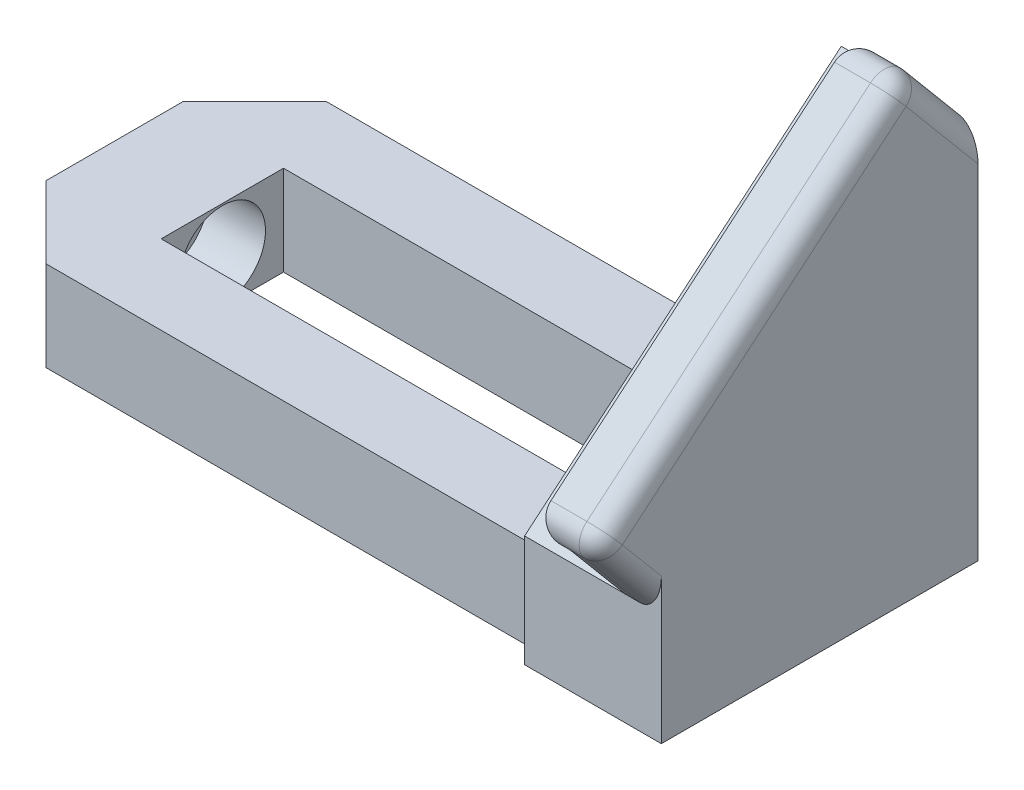
SolidWorks part; units mm, degrees
ref_plane "Front Plane" through (0, 0, 0) normal (0, 0, 1) x (1, 0, 0)
ref_plane "Top Plane" through (0, 0, 0) normal (0, 1, 0) x (1, 0, 0)
ref_plane "Right Plane" through (0, 0, 0) normal (1, 0, 0) x (0, 0, -1)
sketch "Sketch1" plane through (0, 0, 0) normal (0, 1, 0) x (1, 0, 0)
  line L0 (-88, 39) -> (-98, 29)
  line L1 (0, 0) -> (-98, 0)
  line L2 (0, 0) -> (0, 39)
  line L3 (0, 39) -> (-98, 39)
  line L4 (-98, 0) -> (-98, 39)
  line L5 (-19, 11) -> (-83, 11)
  line L6 (-19, 11) -> (-19, 28)
  line L7 (-19, 28) -> (-83, 28)
  line L8 (-83, 11) -> (-83, 28)
  line L9 (-98, 10) -> (-88, 0)
  dimension "D1" = 11
  dimension "D2" = 11
  dimension "D3" = 15
  dimension "D4" = 39
  dimension "D5" = 64
  dimension "D6" = 19
  dimension "D7" = 10
  dimension "D8" = 10
  dimension "D9" = 10
  dimension "D10" = 10
extrude "Boss-Extrude1" add sketch "Sketch1" along normal blind 12.5 contours L4 L9 L1 L2 L3 L0 L5 L8 L7 L6 region at (-44, 0, -37.9452)
sketch "Sketch2" plane through (-83, 0, 0) normal (1, 0, 0) x (0, 0, -1)
  line L0 (28, 12.5) -> (11, 0) construction
  circle A0 centre (19.5, 6.25) radius 6
  dimension "D1" = 12
extrude "Cut-Extrude1" cut sketch "Sketch2" against normal blind 8
sketch "Sketch3" plane through (0, 12.5, 0) normal (0, 1, 0) x (1, 0, 0)
  line L1 (0, 41.5) -> (-19, 41.5)
  line L2 (0, 41.5) -> (0, -2.5)
  line L3 (0, -2.5) -> (-19, -2.5)
  line L4 (-19, 41.5) -> (-19, -2.5)
  line L7 (0, 0) -> (-88, 0) construction
  line L8 (0, 39) -> (-88, 39) construction
  dimension "D1" = 2.5
  dimension "D2" = 2.5
extrude "Boss-Extrude2" add sketch "Sketch3" along normal blind 3 and the other way up to vertex (12.5 mm away) other way up to point (0, 0, 0)
sketch "Sketch4" plane through (0, 0, 0) normal (1, 0, 0) x (0, 0, -1)
  line L0 (41.5, 15.5) -> (41.5, 52.4204)
  line L1 (41.5, 52.4204) -> (-2.5, 15.5)
  line L2 (-2.5, 15.5) -> (41.5, 15.5)
  dimension "D1" = 40
extrude "Boss-Extrude3" add sketch "Sketch4" against normal blind 19
ref_plane "Plane1" through (0, 52.4204, -41.5) normal (0, -0.6428, 0.766) x (1, 0, 0)
sketch "Sketch5" plane through (0, 52.4204, -41.5) normal (0, -0.6428, 0.766) x (1, 0, 0)
  line L0 (0, 0) -> (0, 15)
  line L1 (0, 15) -> (-8, 15)
  line L2 (-8, 15) -> (-6.5, 12)
  line L5 (-5, 0) -> (0, 0)
  line L6 (-6.5, 12) -> (-5, 12)
  line L7 (-5, 12) -> (-5, 0)
  dimension "D1" = 5
  dimension "D2" = 8
  dimension "D3" = 3
  dimension "D4" = 15
  dimension "D5" = 1.5
extrude "Boss-Extrude4" add sketch "Sketch5" along normal up to vertex (57.4379 mm away) up to point (0, 15.5, 2.5)
fillet "Fillet2" radius 0.5 2 edges at (-5, 43.1527, -11.7865) (-5, 33.9602, -19.5)
fillet "Fillet3" radius 3 5 edges at (-4, 63.9111, -31.8582) (0, 45.4509, -9.8582) (-4, 26.9907, 12.1418) (0, 21.2453, 7.3209) (0, 58.1657, -36.6791)
